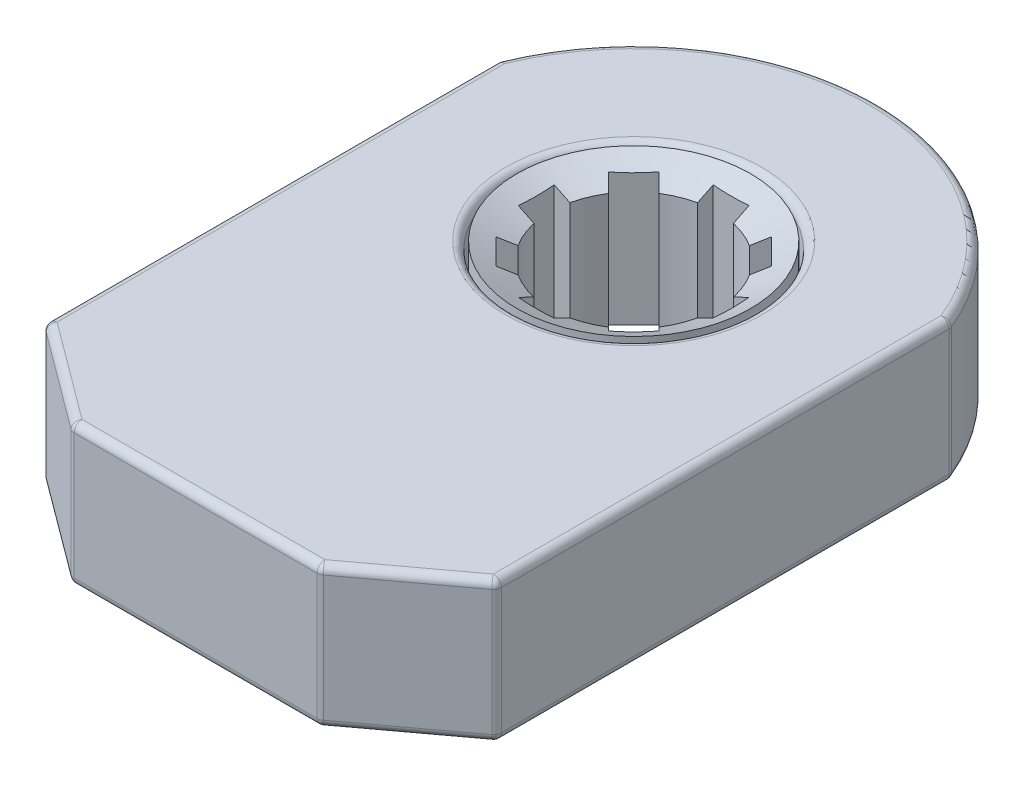
SolidWorks part; units mm, degrees
ref_plane "Front Plane" through (0, 0, 0) normal (0, 0, 1) x (1, 0, 0)
ref_plane "Top Plane" through (0, 0, 0) normal (0, 1, 0) x (1, 0, 0)
ref_plane "Right Plane" through (0, 0, 0) normal (1, 0, 0) x (0, 0, -1)
ref_axis "Axis1" through (0, 9.45, 0) along (0, -1, 0)
sketch "Sketch1" plane through (0, 0, 0) normal (0, 1, 0) x (1, 0, 0)
  line L0 (0, 15.5) -> (0, -27.88) construction
  line L2 (-14.385, 5.7725) -> (-14.385, -27.88)
  line L3 (-14.385, -27.88) -> (14.385, -27.88)
  line L4 (14.385, 5.7725) -> (14.385, -27.88)
  arc A0 (14.385, 5.7725) -> (-14.385, 5.7725) centre (0, 0) ccw
  circle A1 centre (0, 0) radius 7.65
  dimension "D1" = 31
  dimension "D4" = 15.3
  dimension "D2" = 28.77
  dimension "D3" = 43.38
extrude "Boss-Extrude1" add sketch "Sketch1" along normal blind 9
sketch "Sketch3" plane through (0, 9, 0) normal (0, 1, 0) x (1, 0, 0)
  line L0 (0, 0) -> (0, -27.88) construction
  line L1 (-14.385, -27.88) -> (14.385, -27.88) construction
  line L2 (14.385, -23.0642) -> (7.8938, -27.88)
  line L3 (14.385, -27.88) -> (14.385, 5.7725) construction
  line L4 (7.8938, -27.88) -> (14.385, -27.88)
  line L5 (14.385, -27.88) -> (14.385, -23.0642)
  line L6 (-14.385, -27.88) -> (-14.385, -23.0642)
  line L7 (-7.8938, -27.88) -> (-14.385, -27.88)
  line L8 (-14.385, -23.0642) -> (-7.8938, -27.88)
  point P9 (9.1657, -27.88)
  point P12 (14.385, -24.7888)
  point P16 (14.385, -23.0642)
extrude "Cut-Extrude1" cut sketch "Sketch3" against normal blind 9
sketch "Sketch6" plane through (0, 0, 0) normal (1, 0, 0) x (0, 0, -1)
  line L0 (-23.0642, 9) -> (5.7725, 9) construction
  line L2 (-7.4358, 9) -> (-7.4358, 0)
  line L3 (-7.4358, 0) -> (-5.3307, 0)
  line L4 (-5.3307, 7.9438) -> (-5.3307, 0)
  line L5 (-23.0642, 0) -> (5.7725, 0) construction
  line L6 (0, 0) -> (0, 9) construction
  line L7 (-7.4358, 9) -> (-5.3307, 7.9438)
revolve "Revolve1" add sketch "Sketch6" angle 360 about L6
sketch "Sketch7" plane through (0, 0, 0) normal (0, 1, 0) x (1, 0, 0)
  line L1 (-1.1412, 0) -> (1.1412, 0)
  line L2 (-1.1412, 0) -> (-1.1412, 6.2011)
  line L3 (-1.1412, 6.2011) -> (1.1412, 6.2011)
  line L4 (1.1412, 0) -> (1.1412, 6.2011)
extrude "Cut-Extrude2" cut sketch "Sketch7" against normal through all and the other way through all
pattern_circular "CirPattern1" count 8 over 360 about axis through (0, 9.45, 0) along (0, -1, 0) of "Cut-Extrude2"
fillet "Fillet1" radius 0.5 19 edges at (0, 9, -15.5) (0, 0, -15.5) (14.385, 4.5, -5.7725) (14.385, 0, 8.6458) (14.385, 9, 8.6458) (14.385, 4.5, 23.0642) (11.1394, 0, 25.4721) (11.1394, 9, 25.4721) (7.8938, 4.5, 27.88) (0, 0, 27.88) (0, 9, 27.88) (-14.385, 4.5, -5.7725) (-14.385, 9, 8.6458) (-14.385, 0, 8.6458) (-7.8938, 4.5, 27.88) (-11.1394, 0, 25.4721) (-14.385, 4.5, 23.0642) (-11.1394, 9, 25.4721) (0, 9, 7.65)
